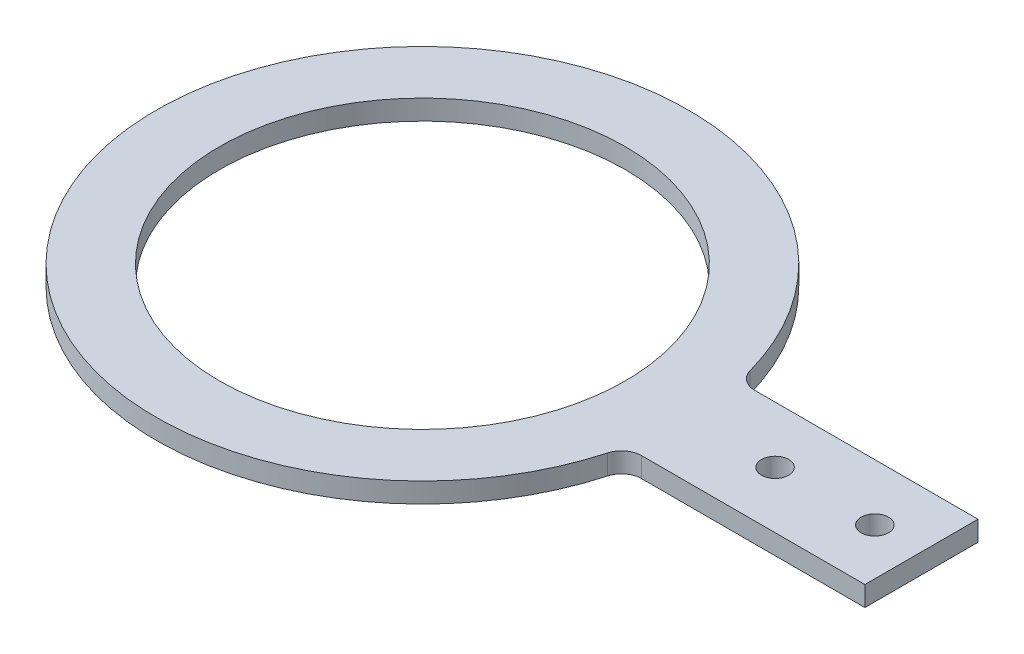
SolidWorks part; units mm, degrees
ref_plane "Front Plane" through (0, 0, 0) normal (0, 0, 1) x (1, 0, 0)
ref_plane "Top Plane" through (0, 0, 0) normal (0, 1, 0) x (1, 0, 0)
ref_plane "Right Plane" through (0, 0, 0) normal (1, 0, 0) x (0, 0, -1)
sketch "Sketch1" plane through (0, 0, 0) normal (0, 1, 0) x (1, 0, 0)
  circle A0 centre (0, 0) radius 40
  circle A1 centre (0, 0) radius 30.5
  dimension "D1" = 80
  dimension "D2" = 61
extrude "Boss-Extrude1" add sketch "Sketch1" along normal blind 3
sketch "Sketch2" plane through (0, 3, 0) normal (0, 1, 0) x (1, 0, 0)
  line L1 (35, 8.5) -> (75, 8.5)
  line L2 (35, 8.5) -> (35, -8.5)
  line L3 (35, -8.5) -> (75, -8.5)
  line L4 (75, 8.5) -> (75, -8.5)
  circle A0 centre (0, 0) radius 30.5 construction
  dimension "D1" = 17
  dimension "D2" = 8.5
  dimension "D3" = 35
  dimension "D4" = 40
extrude "Boss-Extrude2" add sketch "Sketch2" against normal up to surface (3 mm away) up to face at (0, 0, 40)
sketch "Sketch3" plane through (0, 3, 0) normal (0, 1, 0) x (1, 0, 0)
  line L0 (75, -8.5) -> (75, 8.5) construction
  circle A0 centre (53, 0) radius 2.05
  circle A1 centre (68, 0) radius 2.05
  dimension "D1" = 4.1
  dimension "D2" = 15
  dimension "D3" = 7
extrude "Cut-Extrude1" cut sketch "Sketch3" against normal through all
fillet "Fillet1" radius 3 2 edges at (39.0864, 1.5, 8.5) (39.0864, 1.5, -8.5)
